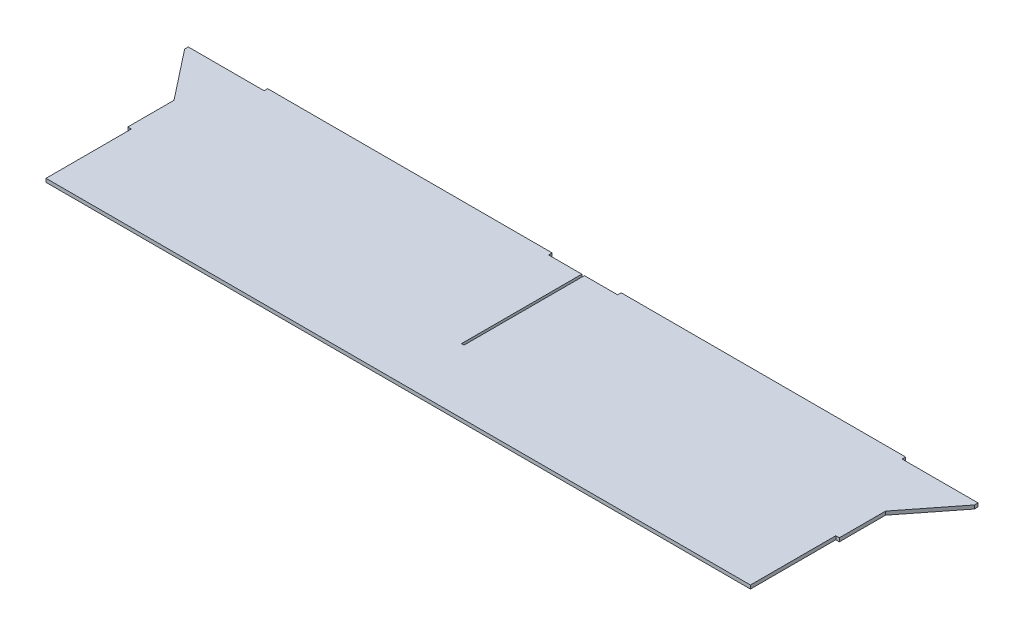
SolidWorks part; units mm, degrees
material "6061-T6 (SS)"
ref_plane "X-Y Datum" through (0, 0, 0) normal (0, 0, 1) x (1, 0, 0)
ref_plane "X-Z Datum" through (0, 0, 0) normal (0, 1, 0) x (1, 0, 0)
ref_plane "Y-Z Datum" through (0, 0, 0) normal (1, 0, 0) x (0, 0, -1)
sketch "Sketch1" plane through (0, 0, 0) normal (0, 1, 0) x (1, 0, 0)
  line L1 (-317.6778, 82.55) -> (317.6778, 82.55)
  line L2 (-317.6778, 82.55) -> (-317.6778, -82.55)
  line L3 (-317.6778, -82.55) -> (317.6778, -82.55)
  line L4 (317.6778, 82.55) -> (317.6778, -82.55)
  line L5 (-317.6778, 82.55) -> (317.6778, -82.55) construction
  line L6 (-317.6778, -82.55) -> (317.6778, 82.55) construction
  point P0 (0, 0)
  dimension "D1" = 635.3556
  dimension "D2" = 165.1
extrude "Boss-Extrude1" add sketch "Sketch1" along normal mid plane 3.175
sketch "Sketch2" plane through (0, 0, -82.55) normal (0, 0, -1) x (-1, 0, 0)
  line L20 (-317.6778, -1.5875) -> (317.6778, -1.5875) construction
  line L21 (-284.8229, -1.5875) -> (-30.8229, -1.5875)
  line L22 (30.8229, -1.5875) -> (284.8229, -1.5875)
  line L40 (30.8229, -1.5875) -> (30.8229, 1.5875)
  line L41 (30.8229, 1.5875) -> (284.8229, 1.5875)
  line L42 (284.8229, 1.5875) -> (284.8229, -1.5875)
  line L56 (-284.8229, -1.5875) -> (-284.8229, 1.5875)
  line L57 (-284.8229, 1.5875) -> (-30.8229, 1.5875)
  line L58 (-30.8229, 1.5875) -> (-30.8229, -1.5875)
extrude "Boss-Extrude2" add sketch "Sketch2" along normal blind 3.175
sketch "Sketch3" plane through (0, -1.5875, 0) normal (0, -1, 0) x (1, 0, 0)
  line L0 (317.6778, -82.55) -> (352.6028, -82.55)
  line L1 (352.6028, -82.55) -> (352.6028, -79.375)
  line L3 (352.6028, -79.375) -> (317.6778, -34.925)
  line L4 (317.6778, 82.55) -> (317.6778, -82.55) construction
  line L17 (317.6778, -82.55) -> (317.6778, 82.55)
  line L18 (317.6778, 82.55) -> (-317.6778, 82.55)
  line L19 (-317.6778, 82.55) -> (-317.6778, -82.55)
  line L20 (-317.6778, -82.55) -> (-284.8229, -82.55)
  line L21 (-284.8229, -82.55) -> (-284.8229, -85.725)
  line L22 (-284.8229, -85.725) -> (-30.8229, -85.725)
  line L23 (-30.8229, -85.725) -> (-30.8229, -82.55)
  line L24 (-30.8229, -82.55) -> (30.8229, -82.55)
  line L25 (30.8229, -82.55) -> (30.8229, -85.725)
  line L26 (30.8229, -85.725) -> (284.8229, -85.725)
  line L27 (284.8229, -85.725) -> (284.8229, -82.55)
  line L28 (284.8229, -82.55) -> (317.6778, -82.55)
  line L29 (317.6778, -82.55) -> (317.6778, -34.925)
  dimension "D1" = 34.925
  dimension "D2" = 3.175
  dimension "D3" = 44.45
  dimension "D4" = 0
extrude "Boss-Extrude3" add sketch "Sketch3" against normal blind 3.175
mirror "Mirror1" about plane through (0, 0, 0) normal (1, 0, 0) of "Boss-Extrude3"
sketch "Sketch4" plane through (0, -1.5875, 0) normal (0, -1, 0) x (1, 0, 0)
  line L0 (-284.4038, 82.55) -> (-284.4038, 71.882)
  line L1 (-317.6778, 82.55) -> (317.6778, 82.55) construction
  line L2 (-284.4038, 71.882) -> (-317.6778, 71.882)
  line L3 (-317.6778, -34.925) -> (-317.6778, 82.55) construction
  circle A0 centre (-284.4038, 71.882) radius 3.675
extrude "Cut-Extrude1" [suppressed] cut sketch "Sketch4" against normal through all contours L2 A0 L0 | L0 A0 L2
pattern_linear "LPattern1" [suppressed] count 5 spacing 139.7 of bodies 107
sketch "Sketch5" plane through (0, -1.5875, 0) normal (0, -1, 0) x (1, 0, 0)
  line L0 (-317.6778, 82.55) -> (317.6778, 82.55) construction
  line L1 (-317.6778, -34.925) -> (-317.6778, 82.55) construction
  line L2 (-317.6778, 82.55) -> (317.6778, 82.55)
  line L3 (-317.6778, -34.925) -> (-317.6778, 82.55)
  line L4 (0, 127.4245) -> (0, -127.4245) construction
  line L5 (-317.6778, 82.55) -> (-314.5028, 82.55)
  line L6 (-317.6778, 82.55) -> (-317.6778, 6.35)
  line L7 (-317.6778, 6.35) -> (-314.5028, 6.35)
  line L8 (-314.5028, 82.55) -> (-314.5028, 6.35)
  line L9 (317.6778, 6.35) -> (314.5028, 6.35)
  line L10 (314.5028, 82.55) -> (314.5028, 6.35)
  line L11 (317.6778, -34.925) -> (317.6778, 82.55)
  line L12 (30.8229, -82.55) -> (-30.8229, -82.55) construction
  line L13 (30.8229, -82.55) -> (-30.8229, -82.55)
  line L14 (-1.143, -85.725) -> (-1.143, -82.55) construction
  line L15 (-1.143, -85.725) -> (-1.143, -82.55)
  line L17 (-1.143, -82.55) -> (1.143, -82.55)
  line L18 (-1.143, -82.55) -> (-1.143, 24.892)
  line L19 (-1.143, 24.892) -> (1.143, 24.892)
  line L20 (1.143, -82.55) -> (1.143, 24.892)
  point P10 (0, 0)
  line M10 (317.6778, -34.925) -> (317.6778, 82.55)
  line M11 (317.6778, 82.55) -> (-317.6778, 82.55)
  line M12 (-317.6778, 82.55) -> (-317.6778, -34.925)
  dimension "D1" = 3.175
  dimension "D2" = 76.2
  dimension "D3" = 2.286
  dimension "D4" = 107.442
extrude "Cut-Extrude2" cut sketch "Sketch5" against normal through all contours L19 L4 L17 L20 | L4 L19 L18 L13 | L8 L2 L7 M12 | L10 L9 M11 M10 region at (316.0903, -1.5875, 44.45) region at (0.5715, -1.5875, -28.829) region at (-0.5715, -1.5875, -28.829) region at (-316.0903, -1.5875, 44.45)
sketch "Sketch6" plane through (0, -1.5875, 0) normal (0, -1, 0) x (1, 0, 0)
  line L0 (-314.5028, 82.55) -> (314.5028, 82.55) construction
  line L1 (-314.5028, 82.55) -> (314.5028, 82.55)
  line L2 (0, 127.6954) -> (0, 37.4046) construction
  point P6 (0, 82.55)
